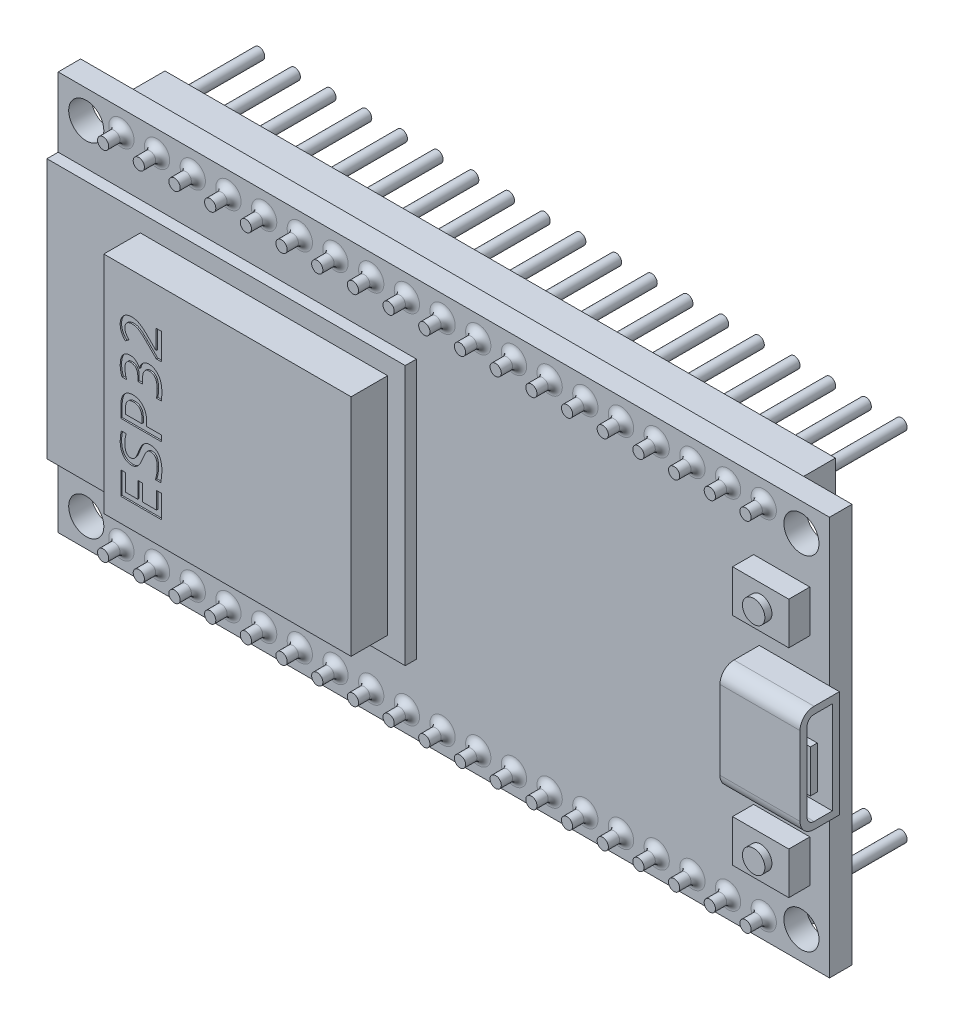
SolidWorks part; units mm, degrees
ref_plane "Front Plane" through (0, 0, 0) normal (0, 0, 1) x (1, 0, 0)
ref_plane "Top Plane" through (0, 0, 0) normal (0, 1, 0) x (1, 0, 0)
ref_plane "Right Plane" through (0, 0, 0) normal (1, 0, 0) x (0, 0, -1)
sketch "Sketch1" plane through (0, 0, 0) normal (0, 0, 1) x (1, 0, 0)
  line L1 (0, 0) -> (54.9, 0)
  line L2 (0, 0) -> (0, 28.4)
  line L3 (0, 28.4) -> (54.9, 28.4)
  line L4 (54.9, 0) -> (54.9, 28.4)
  circle A0 centre (2, 26.4) radius 1.25
  circle A1 centre (52.9, 26.4) radius 1.25
  circle A2 centre (2, 2) radius 1.25
  circle A3 centre (52.9, 2) radius 1.25
  dimension "D3" = 2
  dimension "D1" = 54.9
  dimension "D2" = 28.4
  dimension "D4" = 2
  dimension "D5" = 2
  dimension "D6" = 2
  dimension "D7" = 2
  dimension "D8" = 2
  dimension "D9" = 2
  dimension "D10" = 2
extrude "Boss-Extrude1" add sketch "Sketch1" along normal blind 1.6
sketch "Sketch2" plane through (0, 0, 1.6) normal (0, 0, 1) x (1, 0, 0)
  line L0 (54.9, 0) -> (54.9, 28.4) construction
  line L1 (54.9, 18) -> (49.9, 18)
  line L2 (54.9, 18) -> (55.6, 18)
  line L3 (54.9, 10.4) -> (49.9, 10.4)
  line L4 (49.9, 18) -> (49.9, 10.4)
  line L5 (0, 0) -> (54.9, 0) construction
  line L6 (54.9, 28.4) -> (0, 28.4) construction
  line L7 (55.6, 18) -> (55.6, 10.4)
  line L8 (55.6, 10.4) -> (54.9, 10.4)
  dimension "D1" = 18
  dimension "D2" = 18
  dimension "D3" = 5
  dimension "D4" = 0.7
extrude "Boss-Extrude2" add sketch "Sketch2" along normal blind 2.8
fillet "Fillet1" radius 1 2 edges at (52.75, 18, 4.4) (52.75, 10.4, 4.4)
sketch "Sketch3" plane through (55.6, 0, 0) normal (1, 0, 0) x (0, 0, -1)
  line L5 (-3.6622, 15.6226) -> (-3.173, 15.6226)
  line L6 (-3.6622, 15.6226) -> (-3.6622, 12.5984)
  line L7 (-3.6622, 12.5984) -> (-3.173, 12.5984)
  line L8 (-2.1, 17.5) -> (-3.4, 17.5)
  line L9 (-3.9, 17) -> (-3.9, 11.4)
  line L10 (-3.4, 10.9) -> (-2.1, 10.9)
  line L11 (-2.1, 10.9) -> (-2.1, 17.5)
  line L12 (-2.1, 17.5) -> (-3.4, 17.5)
  line L13 (-3.9, 17) -> (-3.9, 11.4)
  line L14 (-3.4, 10.9) -> (-2.1, 10.9)
  line L15 (-2.1, 10.9) -> (-2.1, 17.5)
  line L16 (-3.173, 15.6226) -> (-3.173, 12.5984)
  arc A4 (-3.4, 17.5) -> (-3.9, 17) centre (-3.4, 17) ccw
  arc A5 (-3.9, 11.4) -> (-3.4, 10.9) centre (-3.4, 11.4) ccw
  arc A6 (-3.4, 17.5) -> (-3.9, 17) centre (-3.4, 17) ccw
  arc A7 (-3.9, 11.4) -> (-3.4, 10.9) centre (-3.4, 11.4) ccw
  dimension "D1" = 0.5
extrude "Cut-Extrude1" cut sketch "Sketch3" against normal blind 5
sketch "Sketch4" plane through (0, 0, 1.6) normal (0, 0, 1) x (1, 0, 0)
  line L0 (0, 14.2) -> (55.6, 14.2) construction
  line L1 (0, 28.4) -> (0, 0) construction
  line L2 (55.6, 11.4) -> (55.6, 17) construction
  line L3 (54.9, 28.4) -> (0, 28.4) construction
  line L4 (49.5, 23.4) -> (53.5, 23.4)
  line L5 (49.5, 23.4) -> (49.5, 20.4)
  line L6 (49.5, 20.4) -> (53.5, 20.4)
  line L7 (53.5, 23.4) -> (53.5, 20.4)
  line L8 (54.9, 18) -> (54.9, 28.4) construction
  line L9 (53.5, 5) -> (53.5, 8)
  line L10 (49.5, 8) -> (53.5, 8)
  line L11 (49.5, 5) -> (49.5, 8)
  line L12 (49.5, 5) -> (53.5, 5)
  dimension "D1" = 4
  dimension "D2" = 3
  dimension "D3" = 8
  dimension "D4" = 5.4
extrude "Boss-Extrude3" add sketch "Sketch4" along normal blind 1.5
sketch "Sketch5" plane through (0, 0, 3.1) normal (0, 0, 1) x (1, 0, 0)
  line L0 (49.5, 23.4) -> (53.5, 20.4) construction
  line L2 (49.5, 8) -> (53.5, 5) construction
  circle A0 centre (51.5, 21.9) radius 0.8
  circle A1 centre (51.5, 6.5) radius 0.8
extrude "Boss-Extrude4" add sketch "Sketch5" along normal blind 0.5
sketch "Sketch6" plane through (0, 0, 1.6) normal (0, 0, 1) x (1, 0, 0)
  line L0 (0, 28.4) -> (0, 0) construction
  line L1 (0, 23.45) -> (25.5, 23.45)
  line L2 (0, 23.45) -> (0, 4.95)
  line L3 (0, 4.95) -> (25.5, 4.95)
  line L4 (25.5, 23.45) -> (25.5, 4.95)
  line L5 (54.9, 28.4) -> (0, 28.4) construction
  dimension "D1" = 25.5
  dimension "D2" = 18.5
  dimension "D3" = 23.45
extrude "Boss-Extrude5" add sketch "Sketch6" along normal blind 0.8
sketch "Sketch7" plane through (0, 0, 2.4) normal (0, 0, 1) x (1, 0, 0)
  line L0 (0, 4.95) -> (25.5, 4.95) construction
  line L1 (6.65, 22.2) -> (24.25, 22.2)
  line L2 (6.65, 22.2) -> (6.65, 6.2)
  line L3 (6.65, 6.2) -> (24.25, 6.2)
  line L4 (24.25, 22.2) -> (24.25, 6.2)
  line L6 (25.5, 4.95) -> (25.5, 23.45) construction
  dimension "D1" = 16
  dimension "D2" = 17.6
  dimension "D3" = 1.25
  dimension "D4" = 1.25
extrude "Boss-Extrude6" add sketch "Sketch7" along normal blind 2.6
sketch "Sketch8" plane through (0, 0, 5) normal (0, 0, 1) x (1, 0, 0)
  line L0 (10.7386, 22.2) -> (10.7386, 6.2) construction
  line L1 (24.25, 22.2) -> (6.65, 22.2) construction
  line L2 (6.65, 6.2) -> (24.25, 6.2) construction
  text T0 "ESP32 " font "Consolas" height in points 11
extrude "Cut-Extrude2" cut sketch "Sketch8" against normal blind 0.1
sketch "Sketch9" plane through (0, 0, 1.6) normal (0, 0, 1) x (1, 0, 0)
  line L0 (0, 26.9) -> (54.9, 26.9) construction
  line L1 (0, 28.4) -> (0, 23.45) construction
  line L2 (54.9, 18) -> (54.9, 28.4) construction
  line L3 (0, 14.2) -> (55.6, 14.2) construction
  line L4 (0, 23.45) -> (0, 4.95) construction
  line L5 (55.6, 11.4) -> (55.6, 17) construction
  line L6 (54.9, 28.4) -> (0, 28.4) construction
  circle A0 centre (4.5, 26.9) radius 0.4
  circle A1 centre (7.04, 26.9) radius 0.4
  circle A2 centre (9.58, 26.9) radius 0.4
  circle A3 centre (12.12, 26.9) radius 0.4
  circle A4 centre (14.66, 26.9) radius 0.4
  circle A5 centre (17.2, 26.9) radius 0.4
  circle A6 centre (19.74, 26.9) radius 0.4
  circle A7 centre (22.28, 26.9) radius 0.4
  circle A8 centre (24.82, 26.9) radius 0.4
  circle A9 centre (27.36, 26.9) radius 0.4
  circle A10 centre (29.9, 26.9) radius 0.4
  circle A11 centre (32.44, 26.9) radius 0.4
  circle A12 centre (34.98, 26.9) radius 0.4
  circle A13 centre (37.52, 26.9) radius 0.4
  circle A14 centre (40.06, 26.9) radius 0.4
  circle A15 centre (42.6, 26.9) radius 0.4
  circle A16 centre (45.14, 26.9) radius 0.4
  circle A17 centre (47.68, 26.9) radius 0.4
  circle A18 centre (50.22, 26.9) radius 0.4
  circle A19 centre (50.22, 1.5) radius 0.4
  circle A20 centre (47.68, 1.5) radius 0.4
  circle A21 centre (45.14, 1.5) radius 0.4
  circle A22 centre (42.6, 1.5) radius 0.4
  circle A23 centre (40.06, 1.5) radius 0.4
  circle A24 centre (37.52, 1.5) radius 0.4
  circle A25 centre (34.98, 1.5) radius 0.4
  circle A26 centre (32.44, 1.5) radius 0.4
  circle A27 centre (29.9, 1.5) radius 0.4
  circle A28 centre (27.36, 1.5) radius 0.4
  circle A29 centre (24.82, 1.5) radius 0.4
  circle A30 centre (22.28, 1.5) radius 0.4
  circle A31 centre (19.74, 1.5) radius 0.4
  circle A32 centre (17.2, 1.5) radius 0.4
  circle A33 centre (14.66, 1.5) radius 0.4
  circle A34 centre (12.12, 1.5) radius 0.4
  circle A35 centre (9.58, 1.5) radius 0.4
  circle A36 centre (7.04, 1.5) radius 0.4
  circle A37 centre (4.5, 1.5) radius 0.4
  dimension "D2" = 4.5
  dimension "D1" = 1.5
  dimension "D3" = 19
extrude "Boss-Extrude7" add sketch "Sketch9" along normal blind 1.3
extrude "Boss-Extrude8" add sketch "Sketch9<2>" against normal blind 9.8
sketch "Sketch9<2>" plane through (0, 0, 1.6) normal (0, 0, 1) x (1, 0, 0) same geometry as "Sketch9"
fillet "Fillet2" radius 0.5 38 edges at (4.1, 26.9, 1.6) (6.64, 26.9, 1.6) (9.18, 26.9, 1.6) (11.72, 26.9, 1.6) (14.26, 26.9, 1.6) (16.8, 26.9, 1.6) (19.34, 26.9, 1.6) (21.88, 26.9, 1.6) (24.42, 26.9, 1.6) (26.96, 26.9, 1.6) (29.5, 26.9, 1.6) (32.04, 26.9, 1.6) (34.58, 26.9, 1.6) (37.12, 26.9, 1.6) (39.66, 26.9, 1.6) (42.2, 26.9, 1.6) (44.74, 26.9, 1.6) (47.28, 26.9, 1.6) (49.82, 26.9, 1.6) (37.12, 1.5, 1.6) (39.66, 1.5, 1.6) (42.2, 1.5, 1.6) (44.74, 1.5, 1.6) (47.28, 1.5, 1.6) (49.82, 1.5, 1.6) (34.58, 1.5, 1.6) (32.04, 1.5, 1.6) (29.5, 1.5, 1.6) (26.96, 1.5, 1.6) (24.42, 1.5, 1.6) (21.88, 1.5, 1.6) (19.34, 1.5, 1.6) (16.8, 1.5, 1.6) (14.26, 1.5, 1.6) (11.72, 1.5, 1.6) (9.18, 1.5, 1.6) (6.64, 1.5, 1.6) (4.1, 1.5, 1.6)
sketch "Sketch10" plane through (0, 0, 0) normal (0, 0, -1) x (-1, 0, 0)
  line L1 (-51.22, 28.16) -> (-3.5, 28.16)
  line L2 (-51.22, 28.16) -> (-51.22, 25.65)
  line L3 (-51.22, 25.65) -> (-3.5, 25.65)
  line L4 (-3.5, 28.16) -> (-3.5, 25.65)
  line L5 (-51.22, 2.76) -> (-3.5, 2.76)
  line L6 (-51.22, 2.76) -> (-51.22, 0.25)
  line L7 (-51.22, 0.25) -> (-3.5, 0.25)
  line L8 (-3.5, 2.76) -> (-3.5, 0.25)
  circle A0 centre (-50.22, 26.9) radius 0.4 construction
  circle A1 centre (-50.22, 1.5) radius 0.4 construction
  circle A2 centre (-4.5, 1.5) radius 0.4 construction
  circle A3 centre (-4.5, 26.9) radius 0.4 construction
  dimension "D5" = 1
  dimension "D6" = 1
  dimension "D7" = 1
  dimension "D1" = 2.51
  dimension "D2" = 1.25
  dimension "D3" = 2.51
  dimension "D4" = 1.25
  dimension "D8" = 1
extrude "Boss-Extrude9" add sketch "Sketch10" along normal blind 2.5
